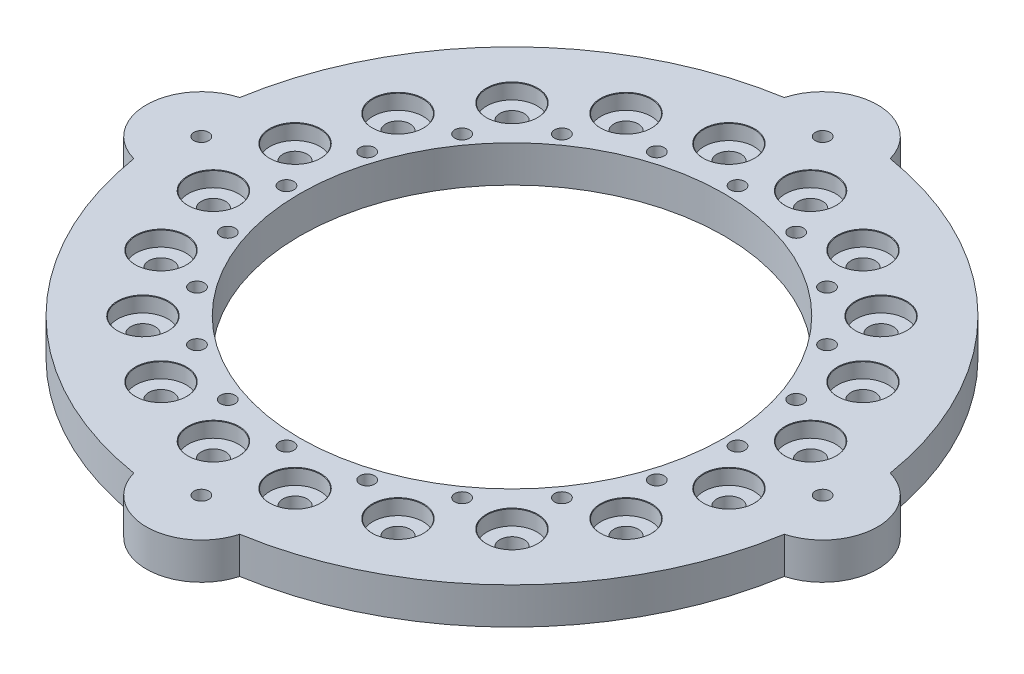
SolidWorks part; units mm, degrees
ref_plane "Front" through (0, 0, 0) normal (0, 0, 1) x (1, 0, 0)
ref_plane "Top" through (0, 0, 0) normal (0, 1, 0) x (1, 0, 0)
ref_plane "Right" through (0, 0, 0) normal (1, 0, 0) x (0, 0, -1)
sketch "Sketch3" plane through (0, 0, 0) normal (0, 1, 0) x (1, 0, 0)
  circle A0 centre (0, 0) radius 114.3
  circle A1 centre (0, 0) radius 73.533
  dimension "D1" = 147.066
  dimension "D2" = 228.6
extrude "Boss-Extrude1" add sketch "Sketch3" along normal blind 12.7
sketch "Sketch4" plane through (0, 12.7, 0) normal (0, 1, 0) x (1, 0, 0)
  circle A0 centre (0, 0) radius 89.8026
  circle A1 centre (0, 0) radius 78.232
  circle A2 centre (0, 0) radius 90.5256
  dimension "D1" = 181.0512
  dimension "D2" = 179.6051
  dimension "D3" = 156.464
ref_axis "Axis1" through (0, 12.7, 0) along (0, -1, 0)
sketch "Sketch7" plane through (0, 12.7, 0) normal (0, 1, 0) x (1, 0, 0)
  line L0 (0, 0) -> (177.5545, 0) construction
  line L1 (0, 0) -> (166.3309, 26.3442) construction
  line L2 (0, 0) -> (157.3635, 51.1305) construction
  dimension "D1" = 9
  dimension "D2" = 9
sketch "Sketch15" plane through (0, 12.7, 0) normal (0, 1, 0) x (1, 0, 0)
  line L0 (107.7631, 0) -> (0, 107.7631)
  line L1 (107.7631, 0) -> (0, -107.7631)
  line L2 (0, 107.7631) -> (-107.7631, 0)
  line L3 (0, -107.7631) -> (-107.7631, 0)
  line L4 (0, 0) -> (177.5545, 0) construction
  dimension "D1" = 152.4
  dimension "D2" = 152.4
  dimension "D3" = 76.2
  dimension "D4" = 76.2
sketch "Sketch16" plane through (0, 12.7, 0) normal (0, 1, 0) x (1, 0, 0)
  circle A0 centre (107.7631, 0) radius 19.05
  dimension "D1" = 38.1
extrude "Boss-Extrude2" add sketch "Sketch16" against normal blind 12.7
pattern_circular "CirPattern6" count 4 over 360 about axis through (0, 12.7, 0) along (0, -1, 0) of "Boss-Extrude2"
hole_wizard "CBORE for 5/16 Binding Head Machine Screw1" positions "Sketch9" profile "Sketch8" counterbore size "5/16" standard "ANSI Inch" end condition through all
sketch "Sketch9" plane through (0, 12.7, 0) normal (0, 1, 0) x (1, 0, 0)
  line L0 (0, 0) -> (166.3309, 26.3442) construction
  circle A0 centre (0, 0) radius 90.5256 construction
  point P0 (89.4111, 14.1613)
sketch "Sketch8" plane through (89.4111, 12.7, -14.1613) normal (1, 0, 0) x (0, 0, 1)
  line L0 (0, 0) -> (0, 12.7)
  line L1 (0, 12.7) -> (4.2164, 12.7)
  line L3 (4.2164, 12.7) -> (4.2164, 5.3086)
  line L4 (8.7312, 5.3086) -> (4.2164, 5.3086)
  line L5 (8.7312, 5.3086) -> (8.7312, 0.1587)
  line L6 (8.7312, 0.1587) -> (8.89, 0)
  line L7 (8.89, 0) -> (0, 0)
  line L8 (-8.7312, 0.1587) -> (-8.89, 0) construction
  line L11 (0, -6.35) -> (0, 107.95) construction
  dimension "Thru Hole Dia." = 8.4328
  dimension "Thru Hole Depth" = 12.7
  dimension "C'Bore Dia." = 17.4625
  dimension "C'Bore Depth" = 5.3086
  dimension "Near C'Sink Dia." = 17.78
  dimension "Near C'Sink Angle" = 90
pattern_circular "CirPattern2" count 20 over 360 about axis through (0, 12.7, 0) along (0, -1, 0) of "CBORE for 5/16 Binding Head Machine Screw1"
hole_wizard "1/4-20 Tapped Hole2" positions "Sketch13" profile "Sketch12" tap size "1/4-20" standard "ANSI Inch" end condition through all
sketch "Sketch13" plane through (0, 12.7, 0) normal (0, 1, 0) x (1, 0, 0)
  line L0 (0, 0) -> (177.5545, 0) construction
  circle A0 centre (0, 0) radius 78.232 construction
  point P0 (78.232, 0)
sketch "Sketch12" plane through (78.232, 12.7, 0) normal (1, 0, 0) x (0, 0, 1)
  line L0 (0, 0) -> (0, 12.7)
  line L1 (0, 12.7) -> (2.5527, 12.7)
  line L2 (2.5527, 12.7) -> (2.5527, 0)
  line L5 (2.5527, 0) -> (0, 0)
  line L11 (0, -6.35) -> (0, 107.95) construction
  dimension "Thru Tap Drill Dia." = 5.1054
  dimension "Thru Tap Drill Depth" = 12.7
cosmetic thread "Hole Thread2" parameters "D2"=6.35
pattern_circular "CirPattern4" count 20 over 360 about axis through (0, 12.7, 0) along (0, -1, 0) of "1/4-20 Tapped Hole2"
hole_wizard "1/4-20 Tapped Hole3" positions "Sketch18" profile "Sketch17" tap size "1/4-20" standard "ANSI Inch" end condition through all
sketch "Sketch18" plane through (0, 12.7, 0) normal (0, 1, 0) x (1, 0, 0)
  point P0 (107.7631, 0)
  point P3 (0, -107.7631)
  point P6 (-107.7631, 0)
  point P9 (0, 107.7631)
sketch "Sketch17" plane through (107.7631, 12.7, 0) normal (1, 0, 0) x (0, 0, 1)
  line L0 (0, 0) -> (0, 12.7)
  line L1 (0, 12.7) -> (2.5527, 12.7)
  line L2 (2.5527, 12.7) -> (2.5527, 0)
  line L5 (2.5527, 0) -> (0, 0)
  line L11 (0, -6.35) -> (0, 107.95) construction
  dimension "Thru Tap Drill Dia." = 5.1054
  dimension "Thru Tap Drill Depth" = 12.7
cosmetic thread "Hole Thread3" parameters "D2"=6.35
cosmetic thread "Hole Thread4" parameters "D2"=6.35
cosmetic thread "Hole Thread5" parameters "D2"=6.35
cosmetic thread "Hole Thread6" parameters "D2"=6.35
